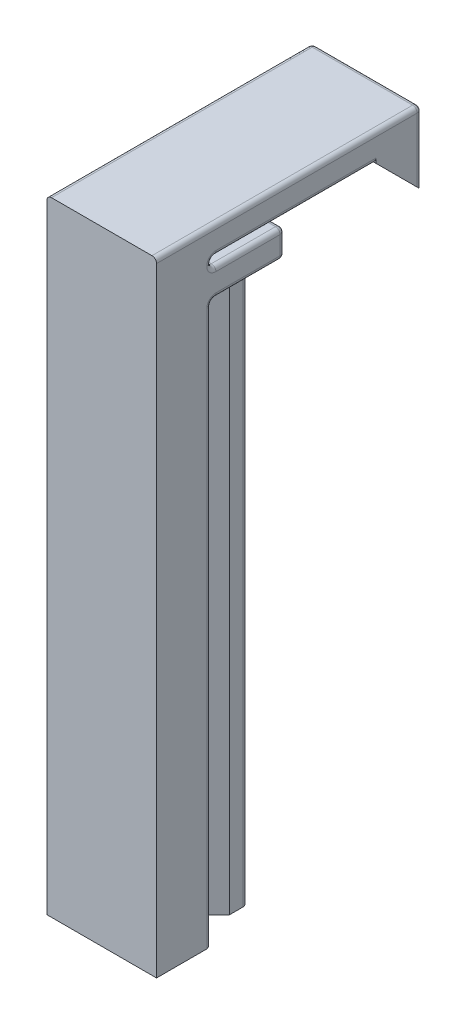
SolidWorks part; units mm, degrees
ref_plane "Plan de face" through (0, 0, 0) normal (0, 0, 1) x (1, 0, 0)
ref_plane "Plan de dessus" through (0, 0, 0) normal (0, 1, 0) x (1, 0, 0)
ref_plane "Plan de droite" through (0, 0, 0) normal (1, 0, 0) x (0, 0, -1)
sketch "Esquisse1" plane through (0, 0, 0) normal (0, 1, 0) x (1, 0, 0)
  line L0 (7.94, 7.96) -> (9.97, 7.96)
  line L1 (0, 0) -> (11.96, 0)
  line L2 (0, 0) -> (0, 5.98)
  line L3 (0, 5.98) -> (4.02, 5.98)
  line L4 (11.96, 0) -> (11.96, 5.98)
  line L6 (4.02, 5.98) -> (4.02, 7.96)
  line L8 (7.94, 5.98) -> (7.94, 7.96)
  line L9 (1.99, 7.96) -> (4.02, 7.96)
  line L10 (1.99, 7.96) -> (1.99, 11.94)
  line L11 (1.99, 11.94) -> (9.97, 11.94)
  line L12 (9.97, 7.96) -> (9.97, 11.94)
  line L13 (7.94, 5.98) -> (11.96, 5.98)
  dimension "D1" = 5.98
  dimension "D2" = 11.96
  dimension "D3" = 4.02
  dimension "D4" = 4.02
  dimension "D5" = 1.98
  dimension "D6" = 3.98
  dimension "D7" = 7.98
  dimension "D8" = 2.03
extrude "Boss.-Extru.1" add sketch "Esquisse1" along normal blind 65
sketch "Esquisse2" plane through (0, 65, 0) normal (0, 1, 0) x (1, 0, 0)
  line L5 (9.97, 11.94) -> (1.99, 11.94) construction
  line L6 (0, 0) -> (11.96, 0)
  line L7 (0, 0) -> (0, 28.94)
  line L8 (0, 28.94) -> (11.96, 28.94)
  line L9 (11.96, 0) -> (11.96, 28.94)
  line L10 (0, 0) -> (11.96, 0) construction
  line L11 (11.96, 0) -> (11.96, 5.98) construction
  line L12 (0, 5.98) -> (0, 0) construction
  dimension "D1" = 17
extrude "Boss.-Extru.2" add sketch "Esquisse2" along normal blind 3
sketch "Esquisse3" plane through (0, 0, -28.94) normal (0, 0, -1) x (-1, 0, 0)
  line L0 (-11.96, 68) -> (0, 68)
  line L1 (-11.96, 68) -> (-11.96, 60)
  line L2 (0, 68) -> (0, 60)
  line L3 (-11.96, 60) -> (0, 60)
  line L4 (-11.96, 65) -> (0, 65) construction
  dimension "D1" = 5
extrude "Boss.-Extru.3" add sketch "Esquisse3" against normal blind 5
chamfer "Chanfrein4" distance 2 angle 45 2 edges at (9.97, 32.5, -7.96) (1.99, 32.5, -7.96)
sketch "Esquisse8" plane through (0, 0, -11.94) normal (0, 0, -1) x (-1, 0, 0)
  line L0 (-1.99, 65) -> (-9.97, 65)
  line L1 (-1.99, 65) -> (-1.99, 60)
  line L2 (-9.97, 65) -> (-9.97, 60)
  line L3 (-1.99, 60) -> (-9.97, 60)
  dimension "D1" = 5
extrude "Enlèv. mat.-Extru.1" cut sketch "Esquisse8" against normal blind 5.96
sketch "Esquisse9" plane through (0, 0, -5.98) normal (0, 0, -1) x (-1, 0, 0)
  line L0 (-4.02, 60) -> (-7.94, 60)
  line L1 (-4.02, 60) -> (-4.02, 65)
  line L2 (-7.94, 60) -> (-7.94, 65)
  line L3 (-4.02, 65) -> (-7.94, 65)
  line L4 (-11.96, 65) -> (0, 65) construction
  point P0 (-5.98, 65)
extrude "Boss.-Extru.5" add sketch "Esquisse9" along normal blind 8
sketch "Esquisse5" plane through (0, 0, -5.98) normal (0, 0, -1) x (-1, 0, 0)
  line L0 (-7.94, 62.5) -> (-11.96, 62.5) construction
  line L1 (-7.94, 65) -> (-7.94, 0) construction
  line L2 (-11.96, 65) -> (-11.96, 0) construction
  line L3 (-11.96, 65) -> (-7.94, 65) construction
  line L4 (0, 65) -> (-11.96, 65) construction
  line L5 (-5.98, 65) -> (-5.98, 0) construction
  line L6 (-10.46, 64) -> (-10.46, 61) construction
  line L7 (-10.46, 64) -> (-11.96, 64)
  line L9 (-11.96, 64) -> (-11.96, 61)
  line L10 (-10.46, 61) -> (-11.96, 61)
  line L11 (-1.5, 61) -> (0, 61)
  line L12 (-11.96, 65) -> (-11.96, 0) construction
  line L13 (0, 64) -> (0, 61)
  line L14 (-1.5, 64) -> (0, 64)
  arc A0 (-10.46, 61) -> (-10.46, 64) centre (-10.46, 62.5) ccw
  arc A2 (-1.5, 61) -> (-1.5, 64) centre (-1.5, 62.5) cw
  dimension "D2" = 3
  dimension "D3" = 1.5
  dimension "D1" = 2.5
extrude "Boss.-Extru.4" add sketch "Esquisse5" along normal blind 8
fillet "Congé2" radius 0.5 40 edges at (2.01, 65, -5.98) (4.02, 65, -9.98) (9.95, 65, -5.98) (7.94, 65, -9.98) (0, 65, -14.96) (0, 68, -14.47) (0, 64, -28.94) (5.98, 68, -28.94) (11.96, 64, -28.94) (11.96, 68, -14.47) (11.96, 65, -14.96) (9.97, 30, -11.94) (1.99, 30, -11.94) (2.01, 0, -5.98) (9.95, 0, -5.98) (5.98, 0, -11.94) (5.98, 65, -13.98) (4.02, 62.5, -13.98) (5.98, 60, -13.98) (7.94, 62.5, -13.98) (0, 64, -9.98) (11.96, 64, -9.98) (11.96, 30.5, -5.98) (0, 30.5, -5.98) (11.21, 61, -5.98) (11.21, 64, -5.98) (0.75, 64, -5.98) (0.75, 61, -5.98) (0.75, 64, -13.98) (0.75, 61, -13.98) (11.21, 61, -13.98) (11.21, 64, -13.98) (0, 61, -9.98) (0, 62.5, -13.98) (11.96, 62.5, -13.98) (11.96, 61, -9.98) (8.96, 62.5, -5.98) (3, 62.5, -5.98) (3, 62.5, -13.98) (8.96, 62.5, -13.98)
chamfer "Chanfrein5" distance 5 angle 45 1 edges at (5.98, 60, -23.94)
